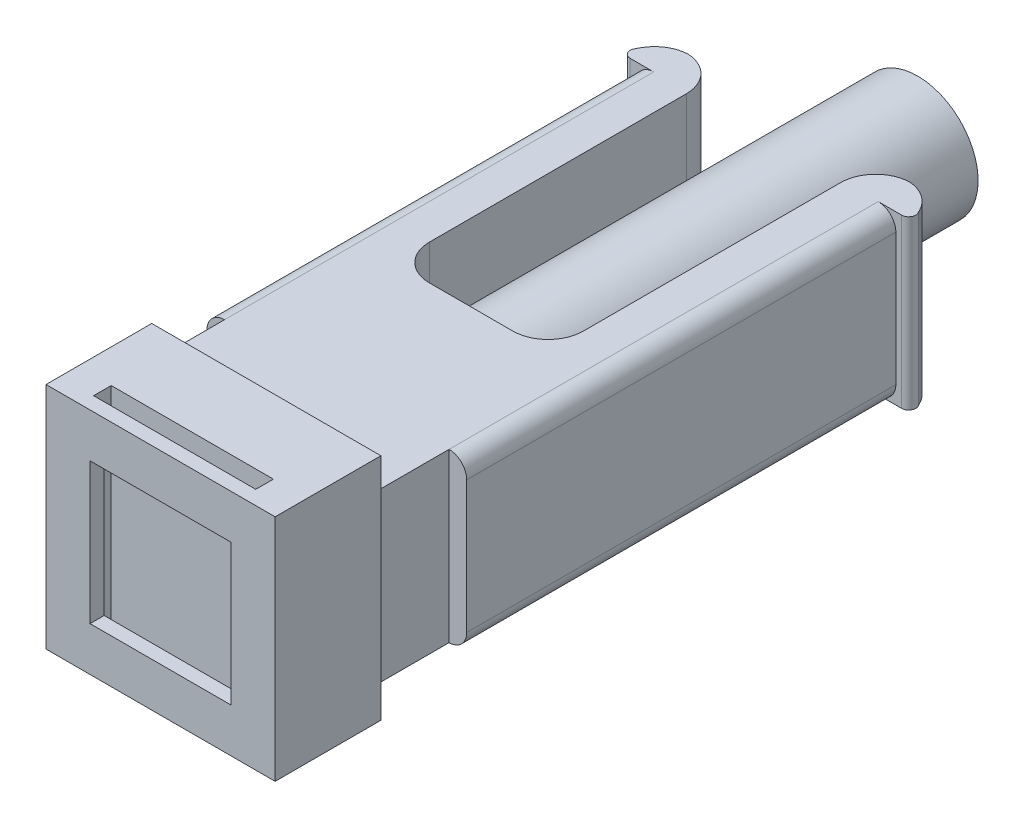
SolidWorks part; units mm, degrees
ref_plane "Front Plane" through (0, 0, 0) normal (0, 0, 1) x (1, 0, 0)
ref_plane "Top Plane" through (0, 0, 0) normal (0, 1, 0) x (1, 0, 0)
ref_plane "Right Plane" through (0, 0, 0) normal (1, 0, 0) x (0, 0, -1)
sketch "Sketch2" plane through (0, 0, 0) normal (0, 1, 0) x (1, 0, 0)
  line L0 (-3.2697, 3.3806) -> (-3.2697, 7.9348)
  line L2 (-3.2697, 3.3806) -> (-3.2697, -4.2394)
  line L3 (-3.2697, -4.2394) -> (4.1003, -4.2394)
  line L4 (4.1003, 5.3164) -> (4.1003, -4.2394)
  line L5 (-3.2697, 3.3806) -> (4.1003, -4.2394) construction
  line L6 (-3.2697, -4.2394) -> (4.1003, 5.3164) construction
  line L7 (-3.2697, 8.8623) -> (-1.7697, 8.8623)
  line L8 (-1.7697, 8.8623) -> (-1.7697, 3.3806)
  line L9 (4.1003, 5.3164) -> (4.1003, 7.9348)
  line L10 (4.1003, 8.8623) -> (2.6003, 8.8623)
  line L11 (2.6003, 8.8623) -> (2.6003, 3.3806)
  line L12 (-3.2697, 8.8623) -> (-3.7697, 7.9348)
  line L13 (-3.7697, 7.9348) -> (-3.2697, 7.9348)
  line L14 (4.1003, 8.8623) -> (4.6003, 7.9348)
  line L15 (4.6003, 7.9348) -> (4.1003, 7.9348)
  line L16 (-1.7697, 3.3806) -> (-1.7697, -0.4294)
  line L17 (-1.7697, -0.4294) -> (2.6003, -0.4294)
  line L18 (2.6003, -0.4294) -> (2.6003, 3.3806)
  point P0 (0, 0)
  dimension "D1" = 7.37
  dimension "D2" = 7.62
  dimension "D3" = 1.5
  dimension "D4" = 1.5
  dimension "D5" = 0.5
  dimension "D6" = 0.5
  dimension "D7" = 3.81
extrude "Boss-Extrude1" add sketch "Sketch2" along normal blind 4.75
fillet "Fillet2" radius 0.2 2 edges at (4.6003, 2.375, -7.9348) (-3.7697, 2.375, -7.9348)
fillet "Fillet3" radius 1 4 edges at (-1.7697, 2.375, -8.8623) (2.6003, 2.375, -8.8623) (4.1003, 2.375, -8.8623) (-3.2697, 2.375, -8.8623)
fillet "Fillet5" radius 0.5 4 edges at (4.1003, 4.75, -1.8477) (-3.2697, 4.75, -1.8477) (-3.2697, 0, -1.8477) (4.1003, 0, -1.8477)
fillet "Fillet6" radius 1 2 edges at (-1.7697, 2.375, 0.4294) (2.6003, 2.375, 0.4294)
sketch "Sketch3" plane through (0, 0, 4.2394) normal (0, 0, 1) x (1, 0, 0)
  line L1 (-2.7697, 0) -> (3.6003, 0)
  line L2 (-2.7697, 0) -> (-2.7697, 4.75)
  line L3 (-2.7697, 4.75) -> (3.6003, 4.75)
  line L4 (3.6003, 0) -> (3.6003, 4.75)
  line L5 (-2.7697, 0) -> (3.6003, 4.75) construction
  line L6 (-2.7697, 4.75) -> (3.6003, 0) construction
  point P4 (0.4153, 2.375)
extrude "Boss-Extrude2" add sketch "Sketch3" along normal blind 2
sketch "Sketch4" plane through (0, 0, 6.2394) normal (0, 0, 1) x (1, 0, 0)
  line L0 (0.4153, 4.75) -> (0.4153, 0) construction
  line L5 (3.6003, 4.75) -> (-2.7697, 4.75) construction
  line L6 (-2.7697, 0) -> (3.6003, 0) construction
  line L8 (-2.8347, -0.875) -> (3.6653, -0.875)
  line L9 (-2.8347, -0.875) -> (-2.8347, 5.625)
  line L10 (-2.8347, 5.625) -> (3.6653, 5.625)
  line L11 (3.6653, -0.875) -> (3.6653, 5.625)
  line L12 (-2.8347, -0.875) -> (3.6653, 5.625) construction
  line L13 (-2.8347, 5.625) -> (3.6653, -0.875) construction
  point P0 (-1.3283, 2)
  point P7 (0.4153, 2.375)
  dimension "D1" = 6.5
  dimension "D2" = 6.5
extrude "Boss-Extrude3" add sketch "Sketch4" along normal blind 3 contours L10 L11 L8 L9
sketch "Sketch5" plane through (0, 5.625, 0) normal (0, 1, 0) x (1, 0, 0)
  line L0 (-2.8347, -9.2394) -> (-2.8347, -8.8394) construction
  line L1 (-2.8347, -9.2394) -> (-2.8347, -6.2394) construction
  line L2 (-2.8347, -8.8394) -> (-1.8847, -8.8394) construction
  line L3 (3.6653, -9.2394) -> (3.6653, -8.8394) construction
  line L4 (-1.8847, -8.8394) -> (2.7153, -8.8394)
  line L5 (-1.8847, -8.8394) -> (-1.8847, -8.3394)
  line L6 (-1.8847, -8.3394) -> (2.7153, -8.3394)
  line L7 (2.7153, -8.8394) -> (2.7153, -8.3394)
  line L8 (-1.8847, -8.8394) -> (2.7153, -8.3394) construction
  line L9 (-1.8847, -8.3394) -> (2.7153, -8.8394) construction
  line L10 (3.6653, -9.2394) -> (3.6653, -6.2394) construction
  line L11 (3.6653, -8.8394) -> (2.7153, -8.8394) construction
  point P9 (0.4153, -8.5894)
  dimension "D1" = 0.4
  dimension "D2" = 0.95
  dimension "D3" = 0.95
  dimension "D4" = 0.4
  dimension "D5" = 0.5
extrude "Cut-Extrude1" cut sketch "Sketch5" against normal blind 6
sketch "Sketch8" plane through (0, 0, 9.2394) normal (0, 0, 1) x (1, 0, 0)
  line L0 (-2.8347, 2.375) -> (3.6653, 2.375) construction
  line L1 (-2.8347, -0.875) -> (-2.8347, 5.625) construction
  line L2 (3.6653, -0.875) -> (3.6653, 5.625) construction
  line L4 (2.4153, 0.375) -> (-1.5847, 0.375)
  line L5 (2.4153, 0.375) -> (2.4153, 4.375)
  line L6 (2.4153, 4.375) -> (-1.5847, 4.375)
  line L7 (-1.5847, 0.375) -> (-1.5847, 4.375)
  line L8 (2.4153, 0.375) -> (-1.5847, 4.375) construction
  line L9 (2.4153, 4.375) -> (-1.5847, 0.375) construction
  point P6 (0.4153, 2.375)
  dimension "D1" = 4
  dimension "D2" = 4
extrude "Cut-Extrude2" cut sketch "Sketch8" against normal blind 0.5
sketch "Sketch9" plane through (0, 0, 0.4294) normal (0, 0, -1) x (-1, 0, 0)
  line L0 (-0.4153, 0) -> (-0.4153, 4.75) construction
  line L1 (-1.6003, 0) -> (0.7697, 0) construction
  line L2 (-1.6003, 4.75) -> (0.7697, 4.75) construction
  circle A0 centre (-0.4153, 2.375) radius 1.7145
extrude "Boss-Extrude4" add sketch "Sketch9" along normal blind 12.668 contours A0
